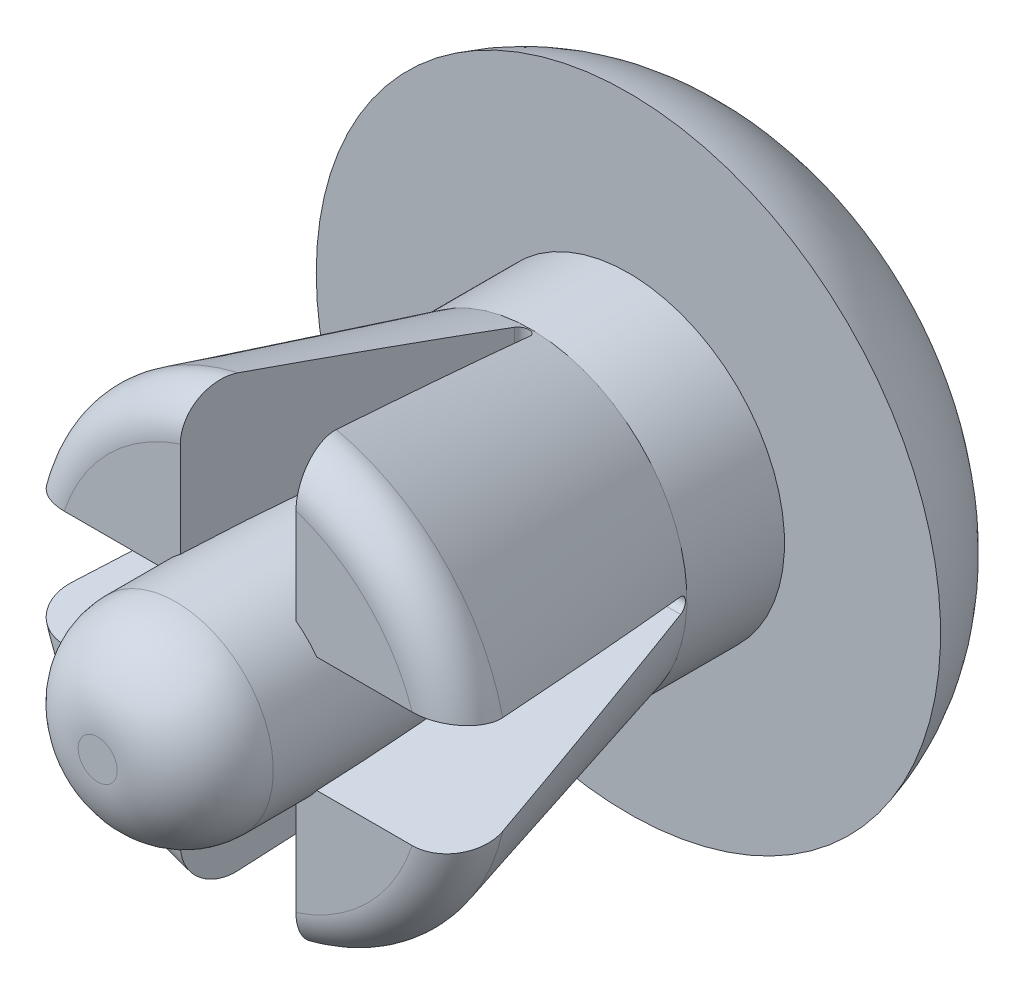
SolidWorks part; units mm, degrees
material "PE Low/Medium Density"
ref_plane "Front Plane" through (0, 0, 0) normal (0, 0, 1) x (1, 0, 0)
ref_plane "Top Plane" through (0, 0, 0) normal (0, 1, 0) x (1, 0, 0)
ref_plane "Right Plane" through (0, 0, 0) normal (1, 0, 0) x (0, 0, -1)
sketch "Sketch1" plane through (0, 0, 0) normal (0, 1, 0) x (1, 0, 0)
  line L0 (0, -6.8) -> (0, 2)
  line L1 (0, 5.0635) -> (0, -10.819) construction
  line L2 (2, 0) -> (4, 0)
  line L3 (2, 0) -> (2, -1.25)
  line L4 (2, -1.25) -> (3, -5)
  line L5 (3, -5) -> (1.25, -5)
  line L6 (1.25, -5) -> (1.25, -6.8)
  line L7 (1.25, -6.8) -> (0, -6.8)
  arc A0 (0, 2) -> (1.9975, 1.8326) centre (0, -10) cw
  arc A1 (1.9975, 1.8326) -> (4, 0) centre (1.5813, -0.6325) cw
  dimension "D5" = 12
  dimension "D6" = 2.5
  dimension "D1" = 2
  dimension "D2" = 8.8
  dimension "D3" = 8
  dimension "D4" = 4
  dimension "D7" = 7
  dimension "D8" = 1.25
  dimension "D9" = 6
  dimension "D10" = 2.5
revolve "Revolve1" add sketch "Sketch1" angle 360 about L1
fillet "Fillet1" radius 1 1 edges at (-1.25, 0, 6.8)
fillet "Fillet2" radius 0.5 1 edges at (-3, 0, 5)
ref_plane "Plane1" through (0, 4, 0) normal (0, 1, 0) x (1, 0, 0)
sketch "Sketch2" plane through (0, 4, 0) normal (0, 1, 0) x (1, 0, 0)
  line L0 (0, 4.7066) -> (0, -12.7867) construction
  line L1 (0, -0.8) -> (0.7406, -5)
  line L2 (0.7406, -5) -> (-0.7406, -5)
  line L3 (0, -0.8) -> (-0.7406, -5)
  line L4 (-2.3492, -5) -> (2.3492, -5) construction
  line L5 (-2, 0) -> (2, 0) construction
  point P7 (0, -5)
  dimension "D1" = 20
  dimension "D2" = 0.8
extrude "Cut-Extrude1" cut sketch "Sketch2" against normal up to surface (2.993 mm away) up to face at (-1.25, 0, 5.8)
fillet "Fillet3" radius 0.1 1 edges at (0, 1.625, 0.8)
pattern_circular "CirPattern1" count 4 over 360 of "Cut-Extrude1", "Fillet3"
